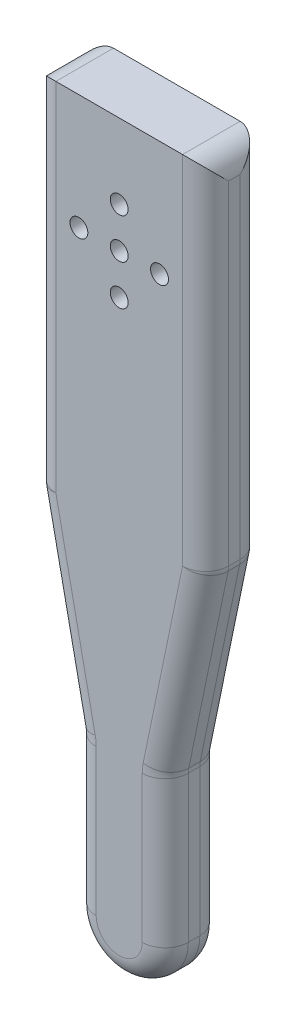
SolidWorks part; units mm, degrees
ref_plane "Front Plane" through (0, 0, 0) normal (0, 0, 1) x (1, 0, 0)
ref_plane "Top Plane" through (0, 0, 0) normal (0, 1, 0) x (1, 0, 0)
ref_plane "Right Plane" through (0, 0, 0) normal (1, 0, 0) x (0, 0, -1)
sketch "Sketch2" plane through (0, 0, 0) normal (0, 0, 1) x (1, 0, 0)
  line L1 (-29.8024, 62.3024) -> (0.1976, 62.3024)
  line L2 (-29.8024, 62.3024) -> (-29.8024, -67.6976)
  line L3 (-29.8024, -67.6976) -> (0.1976, -67.6976)
  line L4 (0.1976, 62.3024) -> (0.1976, -67.6976)
  dimension "D1" = 130
extrude "Boss-Extrude1" add sketch "Sketch2" along normal blind 10
sketch "Sketch3" plane through (0, 0, 10) normal (0, 0, 1) x (1, 0, 0)
  line L0 (-14.8024, 62.3024) -> (-14.8024, 42.3024) construction
  line L1 (0.1976, 62.3024) -> (-29.8024, 62.3024) construction
  line L4 (-29.8024, -67.6976) -> (-21.8024, -67.6976)
  line L5 (-29.8024, -67.6976) -> (-29.8024, 0)
  line L6 (-29.8024, 0) -> (-21.8024, 0)
  line L7 (-21.8024, -67.6976) -> (-21.8024, 0)
  line L9 (0, 0) -> (-7.8024, 0)
  line L10 (0, 0) -> (0, -67.6976)
  line L11 (0, -67.6976) -> (-7.8024, -67.6976)
  line L12 (-7.8024, 0) -> (-7.8024, -67.6976)
  line L13 (-29.8024, -67.6976) -> (0.1976, -67.6976) construction
  circle A0 centre (-14.8024, 42.3024) radius 7 construction
  circle A1 centre (-21.8024, 42.3024) radius 1.55
  circle A2 centre (-14.8024, 49.3024) radius 1.55
  circle A3 centre (-7.8024, 42.3024) radius 1.55
  circle A4 centre (-14.8024, 35.3024) radius 1.55
  circle A5 centre (-14.8024, 42.3024) radius 1.55
  point P5 (-21.8024, 42.3024)
  point P7 (-14.8024, 49.3024)
  point P9 (-7.8024, 42.3024)
  point P11 (-14.8024, 35.3024)
sketch "Sketch6" plane through (0, 0, 10) normal (0, 0, 1) x (1, 0, 0)
  line L1 (-29.8024, -67.6976) -> (-22.8024, -67.6976)
  line L2 (-29.8024, -67.6976) -> (-29.8024, 0)
  line L4 (-22.8024, -67.6976) -> (-22.8024, -33.8488)
  line L11 (0.1976, -67.6976) -> (-6.8024, -67.6976)
  line L12 (0.1976, -67.6976) -> (0.1976, 0)
  line L14 (-6.8024, -67.6976) -> (-6.8024, -33.8488)
  line L15 (-29.8024, 0) -> (-22.8024, -33.8488)
  line L16 (-6.8024, -33.8488) -> (0.1976, 0)
  dimension "D1" = 7
extrude "Cut-Extrude3" cut sketch "Sketch6" against normal through all contours L14 L16 L12 L11 | L4 L15 L2 L1
fillet "Fillet3" 2 edges at (-22.8024, -67.6976, 5) (-6.8024, -67.6976, 5) type full round first side face at (-22.8024, -50.7732, 5) second side face at (-6.8024, -50.7732, 5) middle face at (-14.8024, -67.6976, 5)
fillet "Fillet4" radius 4 20 edges at (-14.8024, -67.6976, 0) (-14.8024, -67.6976, 10) (-6.8024, -46.7732, 0) (-6.8024, -46.7732, 10) (-22.8024, -46.7732, 0) (-22.8024, -46.7732, 10) (0.1976, 31.1512, 10) (0.1976, 62.3024, 5) (0.1976, 31.1512, 0) (0.1976, 0, 5) (-3.3024, -16.9244, 0) (-6.8024, -33.8488, 5) (-3.3024, -16.9244, 10) (-22.8024, -33.8488, 5) (-26.3024, -16.9244, 0) (-26.3024, -16.9244, 10) (-29.8024, 31.1512, 0) (-29.8024, 62.3024, 5) (-29.8024, 31.1512, 10) (-29.8024, 0, 5)
extrude "Cut-Extrude4" cut sketch "Sketch3" against normal through all contours A1 | A4 | A3 | A2 | A5
